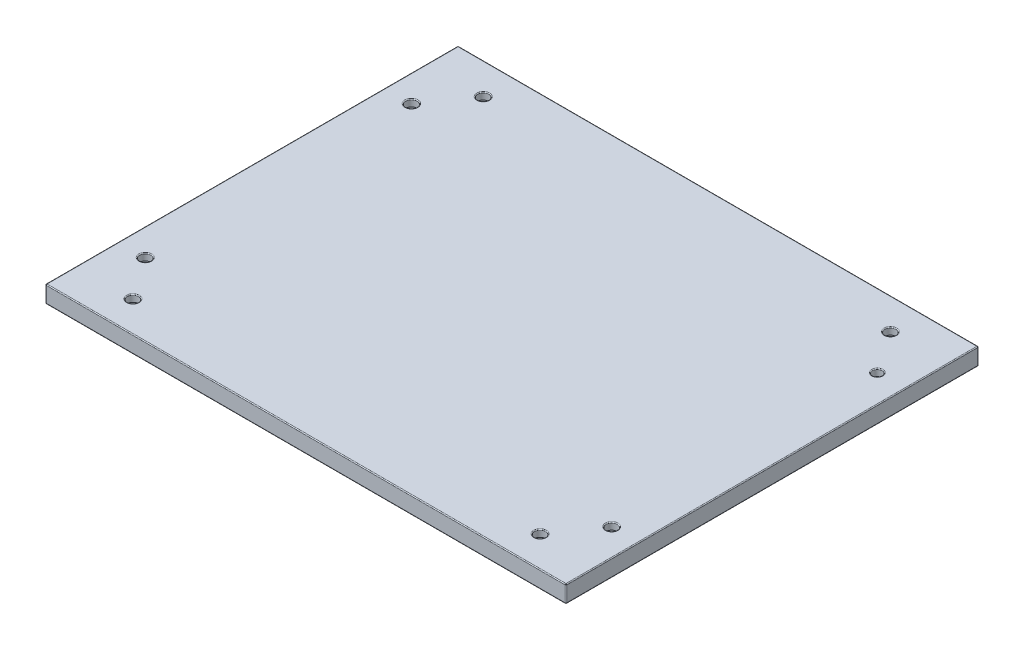
SolidWorks part; units mm, degrees
ref_plane "Front Plane" through (0, 0, 0) normal (0, 0, 1) x (1, 0, 0)
ref_plane "Top Plane" through (0, 0, 0) normal (0, 1, 0) x (1, 0, 0)
ref_plane "Right Plane" through (0, 0, 0) normal (1, 0, 0) x (0, 0, -1)
sketch "Sketch1" plane through (0, 0, 0) normal (0, 1, 0) x (1, 0, 0)
  line L5 (255, -180) -> (0, -180) construction
  line L6 (-269.4171, 199.9914) -> (14.4171, -20.857) construction
  line L7 (0, -180) -> (-255, -180) construction
  line L24 (-8.6985, -12.8573) -> (8.602, 11.6517) construction
  line L40 (-261.8139, 169.8469) -> (-269.4171, 159.143) construction
  line L41 (-261.8139, 169.8469) -> (-263.7589, 167.1086) construction
  line L42 (-8.6985, -12.8573) -> (8.602, 11.6517) construction
  line L45 (-8.6502, 191.6177) -> (-0.1067, 179.212) construction
  line L48 (-246.3498, -12.8914) -> (-263.6502, 11.6177) construction
  line L51 (-246.3498, 191.6177) -> (-248.2318, 188.9681) construction
  line L62 (-246.3498, -12.8914) -> (-246.3498, -9.6414) construction
  line L63 (-263.7589, 167.1086) -> (-260.4002, 167.1086) construction
  line L64 (-237.6394, 167.1086) -> (-217.8631, 167.1086) construction
  line L65 (-240.5829, 169.1864) -> (-237.6394, 167.1086) construction
  line L66 (5.4002, 167.1086) -> (8.2287, 167.1086) construction
  line L71 (14.4171, 199.9914) -> (-269.4171, -20.857) construction
  line L75 (6.6244, 169.4381) -> (14.0358, 158.6764) construction
  line L76 (-14.4171, 209.9914) -> (-279.4171, 209.9914)
  line L83 (-246.3498, 191.6177) -> (-240.5829, 191.6177) construction
  line L84 (-8.6502, 191.6177) -> (-11.1139, 189.498) construction
  line L85 (-217.8631, 167.1086) -> (-246.3498, 191.6177) construction
  line L92 (6.6244, 169.4381) -> (8.2287, 167.1086) construction
  line L97 (-14.4171, 199.9914) -> (-0.1067, 179.212) construction
  line L98 (-0.1067, 179.212) -> (6.1202, 188.0334) construction
  line L103 (-240.5588, 199.7702) -> (-248.2318, 188.9681) construction
  line L104 (-14.4171, -0.6368) -> (-0.0482, -0.6028) construction
  line L109 (14.4171, 19.7873) -> (-14.4171, -20.857) construction
  line L110 (14.4171, -20.857) -> (-0.0482, -0.6028) construction
  line L115 (-240.5829, -21.061) -> (-269.4171, 19.7873) construction
  line L116 (-255, -0.6368) -> (-261.1202, -9.3071) construction
  line L117 (-11.9002, 191.6177) -> (-8.6502, 191.6177) construction
  line L118 (-279.4171, 209.9914) -> (-279.4171, 159.143)
  line L119 (-279.4171, -30.857) -> (-279.4171, 159.143)
  line L120 (-14.4171, -30.857) -> (-279.4171, -30.857)
  line L121 (24.4171, -30.857) -> (-14.4171, -30.857)
  line L122 (24.4171, 19.7873) -> (24.4171, -30.857)
  line L123 (24.4171, 209.9914) -> (24.4171, 19.7873)
  line L124 (-14.4171, 209.9914) -> (24.4171, 209.9914)
  circle A32 centre (-8.6985, -12.8573) radius 3.25
  circle A33 centre (8.602, 11.6517) radius 3.25
  circle A36 centre (-8.6502, 191.6177) radius 3.25
  circle A37 centre (8.2287, 167.1086) radius 2.8284
  circle A40 centre (-246.3498, -12.8914) radius 3.25
  circle A41 centre (-263.6502, 11.6177) radius 3.25
  circle A44 centre (-263.7589, 167.1086) radius 3.3587
  circle A45 centre (-246.3498, 191.6177) radius 3.25
  point P29 (-0.0482, -0.6028)
  point P31 (0, -0.6368)
  point P55 (0, 179.3632)
  point P64 (-255, -0.6368)
  point P73 (-255, 179.3632)
  dimension "D6" = 30
  dimension "D7" = 6.5
  dimension "D8" = 6.5
extrude "Boss-Extrude4" add sketch "Sketch1" along normal blind 10
sketch "Sketch2" plane through (0, 0, 0) normal (0, -1, 0) x (1, 0, 0)
  line L0 (-263.6502, -11.6177) -> (-246.3498, 12.8914) construction
  line L1 (8.6502, -11.6177) -> (-8.6502, 12.8914) construction
  line L2 (-8.6502, -191.6177) -> (8.6502, -167.1086) construction
  line L3 (-246.3498, -191.6177) -> (-263.6502, -167.1086) construction
  line L4 (-127.5, 10.6368) -> (-127.5, -189.3632) construction
  line L5 (-236.6072, 10.6368) -> (-18.3928, 10.6368) construction
  line L6 (-18.3928, -189.3632) -> (-236.6072, -189.3632) construction
  circle A5 centre (-263.6502, -167.1086) radius 5.5
  circle A6 centre (-246.3498, -191.6177) radius 5.5
  circle A7 centre (-246.3498, 12.8914) radius 5.5
  circle A8 centre (-263.6502, -11.6177) radius 5.5
  circle A9 centre (-8.6502, -191.6177) radius 5.5
  circle A10 centre (8.6502, -167.1086) radius 5.5
  circle A11 centre (-8.6502, 12.8914) radius 5.5
  circle A12 centre (8.6502, -11.6177) radius 5.5
  point P13 (-255, 0.6368)
  point P15 (0, 0.6368)
  point P21 (0, -179.3632)
  point P26 (-255, -179.3632)
  dimension "D4" = 11
  dimension "D5" = 11
  dimension "D6" = 11
  dimension "D7" = 11
extrude "Cut-Extrude1" cut sketch "Sketch2" against normal blind 6
fillet "Fillet2" radius 0.5 24 edges at (-279.4171, 0, -89.5672) (-127.5, 0, 30.857) (24.4171, 0, -89.5672) (-127.5, 0, -209.9914) (-263.6502, 0, -172.6086) (8.6502, 0, -161.6086) (-8.6502, 0, 18.3914) (8.6502, 0, -6.1177) (-246.3498, 0, -197.1177) (-246.3498, 0, 7.3914) (-263.6502, 0, -17.1177) (-8.6502, 0, -186.1177) (-246.3498, 10, -188.3677) (-263.7589, 10, -163.7499) (-263.6502, 10, -14.8677) (-246.3498, 10, 9.6414) (8.2287, 10, -169.9371) (-8.6502, 10, -194.8677) (8.602, 10, -8.4017) (-8.6985, 10, 16.1073) (24.4171, 10, -89.5672) (-127.5, 10, 30.857) (-279.4171, 10, -89.5672) (-127.5, 10, -209.9914)
fillet "Fillet3" radius 0.5 12 edges at (24.2706, 9.8536, -209.8449) (24.2706, 0.1464, -209.8449) (-279.2706, 9.8536, -209.8449) (-279.2706, 0.1464, -209.8449) (24.2706, 9.8536, 30.7106) (24.2706, 0.1464, 30.7106) (-279.2706, 9.8536, 30.7106) (-279.2706, 0.1464, 30.7106) (24.4171, 5, -209.9914) (-279.4171, 5, -209.9914) (24.4171, 5, 30.857) (-279.4171, 5, 30.857)
